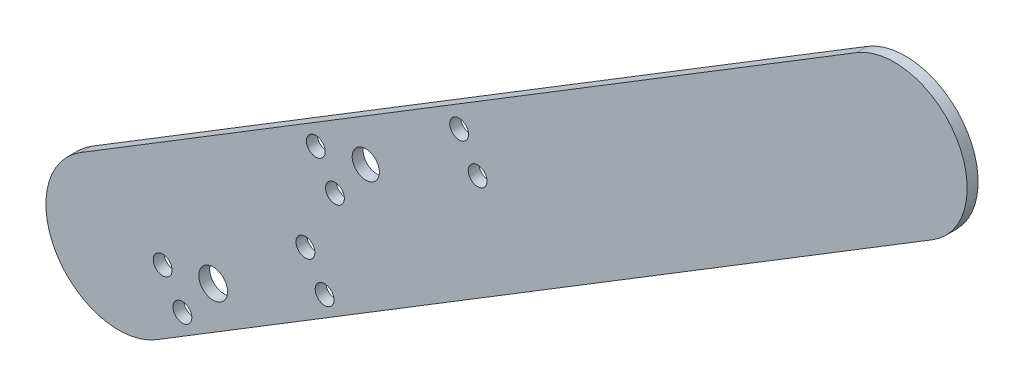
SolidWorks part; units mm, degrees
ref_plane "Front Plane" through (0, 0, 0) normal (0, 0, 1) x (1, 0, 0)
ref_plane "Top Plane" through (0, 0, 0) normal (0, 1, 0) x (1, 0, 0)
ref_plane "Right Plane" through (0, 0, 0) normal (1, 0, 0) x (0, 0, -1)
sketch "Sketch1" plane through (0, 0, 0) normal (0, 0, 1) x (1, 0, 0)
  line L0 (-36.7942, 27.5637) -> (176.4894, 157.9865) construction
  line L1 (-47.228, 44.6264) -> (166.0556, 175.0492)
  line L2 (-26.3604, 10.501) -> (186.9232, 140.9238)
  arc A0 (-47.228, 44.6264) -> (-26.3604, 10.501) centre (-36.7942, 27.5637) ccw
  arc A1 (186.9232, 140.9238) -> (166.0556, 175.0492) centre (176.4894, 157.9865) ccw
  point P2 (69.8476, 92.7751)
base flange "Base-Flange3" sketch "Sketch1" thickness 3 reverse thickness direction no parameters "D1"=3
sketch "Sketch2" plane through (0, 0, 0) normal (0, 0, 1) x (1, 0, 0)
  circle A0 centre (31.1455, 80.9703) radius 3.7317
extrude "Cut-Extrude1" cut sketch "Sketch2" against normal blind 10
hole_wizard "#6 (0.204) Diameter Slot2" positions "Sketch6" profile "Sketch5" size "#6" standard "ANSI Inch" slot yes end condition through all
sketch "Sketch6" plane through (0, 0, -3) normal (0, 0, -1) x (-1, 0, 0)
  point P0 (-17.4079, 78.439)
  point P2 (-22.6711, 69.9047)
sketch "Sketch5" plane through (17.4079, 78.439, -3) normal (1, 0, 0) x (0, 1, 0)
  line L0 (0, 0) -> (0, 3)
  line L1 (0, 3) -> (2.5908, 3)
  line L2 (2.5908, 3) -> (2.5908, 0)
  line L5 (2.5908, 0) -> (0, 0)
  line L11 (0, -6.35) -> (0, 107.95) construction
  dimension "Thru Hole Dia." = 5.1816
  dimension "Thru Hole Depth" = 3
hole_wizard "#6 (0.204) Diameter Slot3" positions "Sketch8" profile "Sketch7" size "#6" standard "ANSI Inch" slot yes end condition through all
sketch "Sketch8" plane through (0, 0, -3) normal (0, 0, -1) x (-1, 0, 0)
  point P0 (-56.8181, 102.2197)
  point P2 (-61.8999, 93.6512)
sketch "Sketch7" plane through (56.8181, 102.2197, -3) normal (1, 0, 0) x (0, 1, 0)
  line L0 (0, 0) -> (0, 3)
  line L1 (0, 3) -> (2.5908, 3)
  line L2 (2.5908, 3) -> (2.5908, 0)
  line L5 (2.5908, 0) -> (0, 0)
  line L11 (0, -6.35) -> (0, 107.95) construction
  dimension "Thru Hole Dia." = 5.1816
  dimension "Thru Hole Depth" = 3
hole_wizard "#6 (0.204) Diameter Slot4" positions "Sketch10" profile "Sketch9" size "#6" standard "ANSI Inch" slot yes end condition through all
sketch "Sketch10" plane through (0, 0, 0) normal (0, 0, 1) x (1, 0, 0)
  point P0 (19.8206, 44.3232)
  point P2 (14.5594, 52.9694)
  point P4 (-19.2706, 20.58)
  point P7 (-24.6928, 29.138)
sketch "Sketch9" plane through (19.8206, 44.3232, 0) normal (1, 0, 0) x (0, -1, 0)
  line L0 (0, 0) -> (0, 3)
  line L1 (0, 3) -> (2.5908, 3)
  line L2 (2.5908, 3) -> (2.5908, 0)
  line L5 (2.5908, 0) -> (0, 0)
  line L11 (0, -6.35) -> (0, 107.95) construction
  dimension "Thru Hole Dia." = 5.1816
  dimension "Thru Hole Depth" = 3
sketch "Sketch11" plane through (0, 0, -3) normal (0, 0, -1) x (-1, 0, 0)
  circle A0 centre (10.8048, 31.6364) radius 3.9623
extrude "Cut-Extrude2" cut sketch "Sketch11" against normal blind 10
sketch "Bend-Lines5" plane through (0, 0, 0) normal (0, 1, 0) x (1, 0, 0)
sketch "Bounding-Box5" plane through (0, 0, 0) normal (0, 1, 0) x (1, 0, 0)
sheet metal parameters "Sheet-Metal3" thickness 3 parameters "D1"=3
flat pattern "Flat-Pattern3" [suppressed]
sketch "Bend-Lines6" plane through (0, 0, 0) normal (0, 1, 0) x (1, 0, 0)
sketch3d "Bounding-Box6" [suppressed]
  line L0 (-6.6289, -27.4965, 0) -> (240.7801, 123.7939, 0) construction
  line L1 (-27.4965, 6.6289, 0) -> (219.9125, 157.9193, 0) construction
  line L2 (-6.6289, -27.4965, 0) -> (-27.4965, 6.6289, 0) construction
  line L3 (240.7801, 123.7939, 0) -> (219.9125, 157.9193, 0) construction
sheet metal parameters "Sheet-Metal4" thickness 3 parameters "D1"=3
flat pattern "Flat-Pattern3"
sketch "Bend-Lines6" plane through (0, 0, 0) normal (0, 1, 0) x (1, 0, 0)
sketch3d "Bounding-Box6" [suppressed]
  line L0 (-6.6289, -27.4965, 0) -> (240.7801, 123.7939, 0) construction
  line L1 (-27.4965, 6.6289, 0) -> (219.9125, 157.9193, 0) construction
  line L2 (-6.6289, -27.4965, 0) -> (-27.4965, 6.6289, 0) construction
  line L3 (240.7801, 123.7939, 0) -> (219.9125, 157.9193, 0) construction
sheet metal parameters "Sheet-Metal6" thickness 3 parameters "D1"=3
flat pattern "Flat-Pattern3"
sketch "Bend-Lines6" plane through (0, 0, 0) normal (0, 1, 0) x (1, 0, 0)
sketch3d "Bounding-Box6" [suppressed]
  line L0 (-6.6289, -27.4965, 0) -> (240.7801, 123.7939, 0) construction
  line L1 (-27.4965, 6.6289, 0) -> (219.9125, 157.9193, 0) construction
  line L2 (-6.6289, -27.4965, 0) -> (-27.4965, 6.6289, 0) construction
  line L3 (240.7801, 123.7939, 0) -> (219.9125, 157.9193, 0) construction
sheet metal parameters "Sheet-Metal7" thickness 3 parameters "D1"=3
flat pattern "Flat-Pattern3"
sketch "Bend-Lines6" plane through (0, 0, 0) normal (0, 1, 0) x (1, 0, 0)
sketch3d "Bounding-Box6" [suppressed]
  line L0 (-6.6289, -27.4965, 0) -> (240.7801, 123.7939, 0) construction
  line L1 (-27.4965, 6.6289, 0) -> (219.9125, 157.9193, 0) construction
  line L2 (-6.6289, -27.4965, 0) -> (-27.4965, 6.6289, 0) construction
  line L3 (240.7801, 123.7939, 0) -> (219.9125, 157.9193, 0) construction
sheet metal parameters "Sheet-Metal8" thickness 3 parameters "D1"=3
flat pattern "Flat-Pattern3"
sketch "Bend-Lines6" plane through (0, 0, 0) normal (0, 1, 0) x (1, 0, 0)
sketch3d "Bounding-Box6" [suppressed]
  line L0 (-6.6289, -27.4965, 0) -> (240.7801, 123.7939, 0) construction
  line L1 (-27.4965, 6.6289, 0) -> (219.9125, 157.9193, 0) construction
  line L2 (-6.6289, -27.4965, 0) -> (-27.4965, 6.6289, 0) construction
  line L3 (240.7801, 123.7939, 0) -> (219.9125, 157.9193, 0) construction
sheet metal parameters "Sheet-Metal9" thickness 3 parameters "D1"=3
flat pattern "Flat-Pattern3"
sketch "Bend-Lines6" plane through (0, 0, 0) normal (0, 1, 0) x (1, 0, 0)
sketch3d "Bounding-Box6" [suppressed]
  line L0 (-6.6289, -27.4965, 0) -> (240.7801, 123.7939, 0) construction
  line L1 (-27.4965, 6.6289, 0) -> (219.9125, 157.9193, 0) construction
  line L2 (-6.6289, -27.4965, 0) -> (-27.4965, 6.6289, 0) construction
  line L3 (240.7801, 123.7939, 0) -> (219.9125, 157.9193, 0) construction
